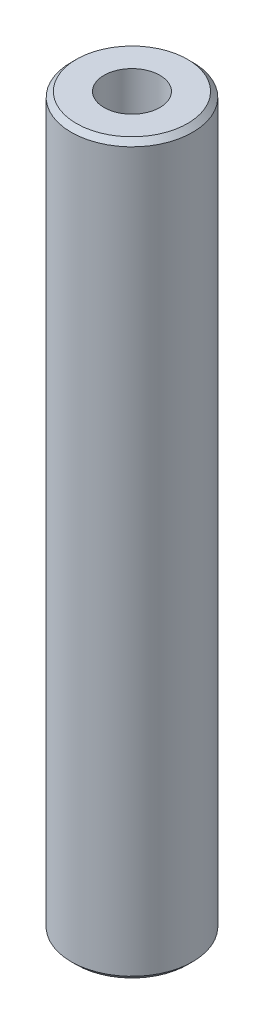
SolidWorks part; units mm, degrees
ref_plane "Front Plane" through (0, 0, 0) normal (0, 0, 1) x (1, 0, 0)
ref_plane "Top Plane" through (0, 0, 0) normal (0, 1, 0) x (1, 0, 0)
ref_plane "Right Plane" through (0, 0, 0) normal (1, 0, 0) x (0, 0, -1)
sketch "Sketch1" plane through (0, 0, 0) normal (0, 1, 0) x (1, 0, 0)
  circle A0 centre (0, 0) radius 50
  dimension "SHAFT_OD" = 100
extrude "Boss-Extrude1" add sketch "Sketch1" along normal blind 600
sketch "Sketch2" plane through (0, 0, 0) normal (0, 1, 0) x (1, 0, 0)
  circle A0 centre (0, 0) radius 23.0156
  dimension "BORE_D" = 46.0313
extrude "Cut-Extrude1" cut sketch "Sketch2" along normal through all
chamfer "Chamfer1" distance 4.2038 angle 45 2 edges at (0, 600, 50) (0, 0, 50)
